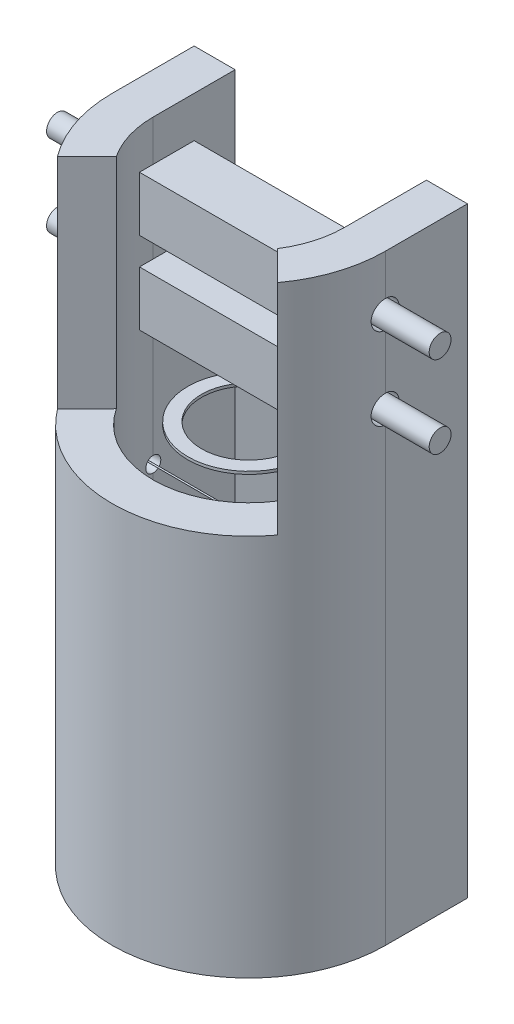
SolidWorks part; units mm, degrees
ref_plane "Front Plane" through (0, 0, 0) normal (0, 0, 1) x (1, 0, 0)
ref_plane "Top Plane" through (0, 0, 0) normal (0, 1, 0) x (1, 0, 0)
ref_plane "Right Plane" through (0, 0, 0) normal (1, 0, 0) x (0, 0, -1)
sketch "Sketch1" plane through (0, 0, 0) normal (0, 1, 0) x (1, 0, 0)
  circle A0 centre (0, 0) radius 17.3
  circle A1 centre (0, 0) radius 22.3
  dimension "D1" = 34.6
  dimension "D2" = 5
extrude "Boss-Extrude1" add sketch "Sketch1" along normal blind 1
sketch "Sketch3" plane through (0, 0, 0) normal (0, 1, 0) x (1, 0, 0)
  line L0 (0, 0) -> (67.2777, 0) construction
  line L1 (0, 0) -> (0, 24.0316) construction
  line L2 (0, 0) -> (-64.1352, 0) construction
  line L3 (-50, 0) -> (-50, 30)
  line L4 (35, -40) -> (50, -40) construction
  line L5 (35, -40) -> (35, 40) construction
  line L6 (35, 40) -> (50, 40) construction
  line L7 (50, -40) -> (50, 40) construction
  line L8 (35, -40) -> (50, 40) construction
  line L9 (35, 40) -> (50, -40) construction
  line L10 (-50, -40) -> (-35, -40) construction
  line L11 (-50, -40) -> (-50, 40) construction
  line L12 (-50, 40) -> (-35, 40) construction
  line L13 (-35, -40) -> (-35, 40) construction
  line L14 (-50, -40) -> (-35, 40) construction
  line L15 (-50, 40) -> (-35, -40) construction
  line L16 (-50, 30) -> (-35, 30) construction
  line L17 (-35, 30) -> (-35, 0)
  line L18 (50, 0) -> (50, 30)
  line L19 (50, 30) -> (35, 30) construction
  line L20 (35, 30) -> (35, 0)
  line L21 (-50, 30) -> (-35, 40)
  line L22 (-50, 30) -> (-35, 30)
  line L23 (-35, 40) -> (-20, 40)
  line L24 (-35, 30) -> (-20, 40)
  line L25 (-35, 30) -> (-35, 0)
  line L26 (50, 30) -> (35, 40)
  line L27 (50, 30) -> (35, 30)
  line L28 (35, 40) -> (20, 40)
  line L29 (35, 30) -> (20, 40)
  arc A0 (50, 0) -> (-50, 0) centre (0, 0) cw
  arc A1 (35, 0) -> (-35, 0) centre (0, 0) cw
  point P4 (42.5, 0)
  point P8 (-42.5, 0)
  dimension "D1" = 35
  dimension "D2" = 35
  dimension "D3" = 15
  dimension "D4" = 15
  dimension "D5" = 40
  dimension "D6" = 40
  dimension "D7" = 30
  dimension "D8" = 30
  dimension "D9" = 50
extrude "Boss-Extrude5" add sketch "Sketch3" against normal blind 140 and the other way blind 80 separate body contours L20 A1 L17 L22 L3 A0 L18 L27 region at (-48.7194, 0, -15)
extrude "Boss-Extrude6" add sketch "Sketch3<10>" against normal blind 140 contours L22 L24 L23 L21 | L29 L27 L26 L28 region at (-35, 0, -35) region at (35, 0, -35)
sketch "Sketch3<10>" plane through (0, 0, 0) normal (0, 1, 0) x (1, 0, 0) same geometry as "Sketch3"
sketch "Sketch6" plane through (-35, 0, 0) normal (1, 0, 0) x (0, 0, -1)
  line L0 (0, -36.4102) -> (0, -142.9955) construction
  circle A0 centre (0, -30) radius 2.8
  circle A1 centre (0, -130) radius 2.8
  dimension "D1" = 5.6
  dimension "D2" = 5.6
  dimension "D5" = 100
  dimension "D6" = 30
extrude "Cut-Extrude1" cut sketch "Sketch6" along normal blind 80 and the other way blind 10
sketch "Sketch10" plane through (35, 0, 0) normal (-1, 0, 0) x (0, 0, 1)
  line L0 (0, -67.9259) -> (0, -124.9829) construction
  circle A0 centre (0, -30) radius 0.25
  circle A1 centre (0, -130) radius 0.25
  dimension "D3" = 0.5
  dimension "D4" = 0.5
  dimension "D1" = 100
  dimension "D2" = 30
extrude "Boss-Extrude7" add sketch "Sketch10" along normal blind 80 and the other way blind 10
sketch "Sketch11" plane through (0, 0, 0) normal (1, 0, 0) x (0, 0, -1)
  line L0 (0, 0) -> (0, 94.1655) construction
  circle A0 centre (0, 60) radius 5
  circle A1 centre (0, 30) radius 5
  dimension "D2" = 10
  dimension "D4" = 10
  dimension "D1" = 60
  dimension "D3" = 30
extrude "Cut-Extrude2" cut sketch "Sketch11" against normal mid plane 1000
sketch "Sketch12" plane through (50, 0, 0) normal (1, 0, 0) x (0, 0, -1)
  line L0 (0, 0) -> (0, 120) construction
  circle A2 centre (0, 30) radius 4
  circle A3 centre (0, 60) radius 4
  dimension "D3" = 8
  dimension "D4" = 8
  dimension "D1" = 30
  dimension "D2" = 60
sketch "Sketch13" plane through (0, 80, 0) normal (0, 1, 0) x (1, 0, 0)
  line L0 (-40, -30) -> (-29.2857, -19.1663)
  line L1 (29.4219, -18.9566) -> (40.1863, -29.75)
  line L2 (45, 0.25) -> (-45, 0.25) construction
  arc A0 (-35, 0) -> (34.9991, 0.25) centre (0, 0) ccw
  arc A1 (-35, 0) -> (35, 0) centre (0, 0) ccw construction
  arc A2 (49.9994, 0.25) -> (-50, 0) centre (0, 0) cw
  arc A3 (-50, 0) -> (50, 0) centre (0, 0) ccw construction
  arc M2 (35, 0) -> (-35, 0) centre (0, 0) cw
  arc M6 (-50, 0) -> (50, 0) centre (0, 0) ccw
  dimension "D1" = 15
  dimension "D2" = 20
  dimension "D3" = 20
  dimension "D4" = 30
  dimension "D5" = 30
extrude "Cut-Extrude3" cut sketch "Sketch13" against normal blind 80 contours L1 L0 M2 M6 region at (0.1206, 80, 36.6286)
extrude "Boss-Extrude8" add sketch "Sketch12" along normal blind 20 and the other way blind 20 separate body
sketch "Sketch14" plane through (-50, 0, 0) normal (-1, 0, 0) x (0, 0, 1)
  circle A0 centre (0, 60) radius 4
  circle A1 centre (0, 30) radius 4
  dimension "D1" = 8
  dimension "D2" = 8
extrude "Boss-Extrude9" add sketch "Sketch14" along normal blind 20 and the other way blind 20 separate body
sketch "Sketch15" plane through (-30, 0, 0) normal (1, 0, 0) x (0, 0, -1)
  line L1 (-10, 70) -> (10, 70)
  line L2 (-10, 70) -> (-10, 50)
  line L3 (-10, 50) -> (10, 50)
  line L4 (10, 70) -> (10, 50)
  line L5 (-10, 70) -> (10, 50) construction
  line L6 (-10, 50) -> (10, 70) construction
  line L7 (-10, 20) -> (10, 20)
  line L8 (-10, 20) -> (-10, 40)
  line L9 (-10, 40) -> (10, 40)
  line L10 (10, 20) -> (10, 40)
  line L11 (-10, 20) -> (10, 40) construction
  line L12 (-10, 40) -> (10, 20) construction
  point P0 (0, 60)
  point P6 (0, 30)
  dimension "D1" = 20
  dimension "D2" = 20
  dimension "D3" = 20
  dimension "D4" = 20
extrude "Boss-Extrude10" add sketch "Sketch15" along normal blind 60
